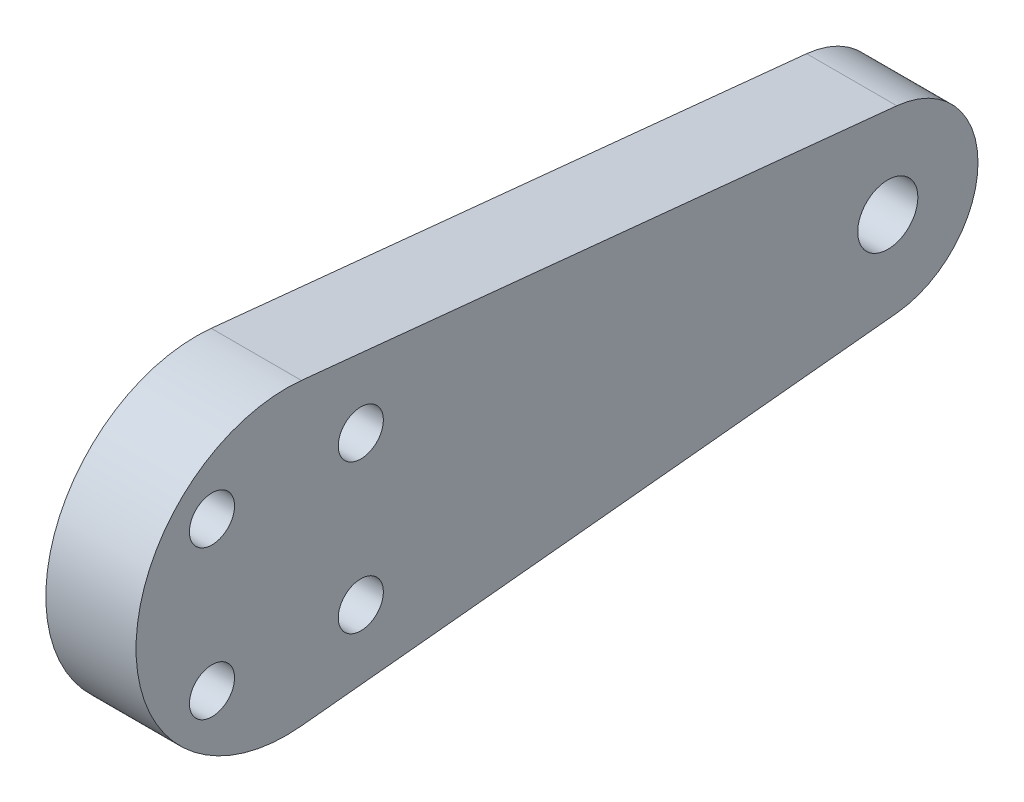
SolidWorks part; units mm, degrees
ref_plane "Front Plane" through (0, 0, 0) normal (0, 0, 1) x (1, 0, 0)
ref_plane "Top Plane" through (0, 0, 0) normal (0, 1, 0) x (1, 0, 0)
ref_plane "Right Plane" through (0, 0, 0) normal (1, 0, 0) x (0, 0, -1)
sketch "length (ref to equation file)" plane through (0, 0, 0) normal (1, 0, 0) x (0, 0, -1)
  line L0 (0, 0) -> (40, 0)
  dimension "D1" = 40
ref_axis "motor pivot" through (0, 0, 0) along (1, 0, 0)
ref_axis "pivot w/ link 2" through (0, 0, -40) along (1, 0, 0)
sketch "Sketch1" plane through (0, 0, 0) normal (1, 0, 0) x (0, 0, -1)
  line L3 (40.6, 5.9699) -> (1, 9.9499)
  line L4 (40.6, -5.9699) -> (1, -9.9499)
  circle A2 centre (0, 0) radius 10
  circle A3 centre (40, 0) radius 6
  arc A4 (7.0711, 7.0711) -> (-7.0711, -7.0711) centre (0, 0) ccw construction
  dimension "D1" = 12
extrude "Boss-Extrude1" add sketch "Sketch1" along normal mid plane 6 contours A2 | A3 L3 A2 L4 | A3
sketch "Sketch2" plane through (0, 0, 0) normal (1, 0, 0) x (0, 0, -1)
  arc A0 (-3.8891, -3.8891) -> (-6.0104, -6.0104) centre (-4.9497, -4.9497) ccw construction
  arc A1 (-6.0104, -6.0104) -> (-3.8891, -3.8891) centre (-4.9497, -4.9497) ccw construction
  arc A2 (6.0104, -3.8891) -> (3.8891, -6.0104) centre (4.9497, -4.9497) ccw construction
  arc A3 (3.8891, -6.0104) -> (6.0104, -3.8891) centre (4.9497, -4.9497) ccw construction
  arc A4 (-6.0104, 3.8891) -> (-3.8891, 6.0104) centre (-4.9497, 4.9497) ccw construction
  arc A5 (-3.8891, 6.0104) -> (-6.0104, 3.8891) centre (-4.9497, 4.9497) ccw construction
  arc A6 (6.0104, 6.0104) -> (3.8891, 3.8891) centre (4.9497, 4.9497) ccw construction
  arc A7 (3.8891, 3.8891) -> (6.0104, 6.0104) centre (4.9497, 4.9497) ccw construction
  arc A8 (-3.8891, -3.8891) -> (-6.0104, -6.0104) centre (-4.9497, -4.9497) ccw construction
  arc A9 (-6.0104, -6.0104) -> (-3.8891, -3.8891) centre (-4.9497, -4.9497) ccw construction
  arc A10 (6.0104, -3.8891) -> (3.8891, -6.0104) centre (4.9497, -4.9497) ccw construction
  arc A11 (3.8891, -6.0104) -> (6.0104, -3.8891) centre (4.9497, -4.9497) ccw construction
  arc A12 (-6.0104, 3.8891) -> (-3.8891, 6.0104) centre (-4.9497, 4.9497) ccw construction
  arc A13 (-3.8891, 6.0104) -> (-6.0104, 3.8891) centre (-4.9497, 4.9497) ccw construction
  arc A14 (6.0104, 6.0104) -> (3.8891, 3.8891) centre (4.9497, 4.9497) ccw construction
  arc A15 (3.8891, 3.8891) -> (6.0104, 6.0104) centre (4.9497, 4.9497) ccw construction
  circle A16 centre (4.9497, 4.9497) radius 1.5
  circle A17 centre (4.9497, -4.9497) radius 1.5
  circle A18 centre (-4.9497, -4.9497) radius 1.5
  circle A19 centre (-4.9497, 4.9497) radius 1.5
extrude "Cut-Extrude1" cut sketch "Sketch2" against normal through all both and the other way through all
sketch "Sketch3" plane through (3, 0, 0) normal (1, 0, 0) x (0, 0, -1)
  circle A0 centre (40, 0) radius 3
  point P0 (40, 0)
  dimension "D1" = 6
hole_wizard "Ø4.0mm Dowel Hole1" positions "Sketch3" profile "Sketch4" hole size "Ø4.0" standard "ANSI Metric" end condition through all
sketch "Sketch4" plane through (3, 0, -40) normal (0, 1, 0) x (0, 0, -1)
  line L0 (0, 0) -> (0, 6)
  line L1 (0, 6) -> (2, 6)
  line L2 (2, 6) -> (2, 0)
  line L5 (2, 0) -> (0, 0)
  line L11 (0, -6.35) -> (0, 107.95) construction
  dimension "Thru Hole Dia." = 4
  dimension "Thru Hole Depth" = 6
equation "\"link 1\" = 40mm"
equation "\"D1@length (ref to equation file)\" = \"link 1\""
equation "\"link 1 thickness\" = 6mm"
equation "\"D1@Boss-Extrude1\"=\"link 1 thickness\""
equation "\"motor center z\" = 60mm"
equation "\"motor center y\" = 20mm"
equation "\"link 2\"= 90mm"
equation "\"pivot height\"= 100mm"
equation "\"beam length\"= 400mm"
equation "\"camera height\"= 250mm"
equation "\"link height\" = 12mm"
equation "\"beam width\"= 28.5mm"
equation "\"beam side wall thickness\"= 3mm"
equation "\"D1@Sketch1\"=\"link height\""
